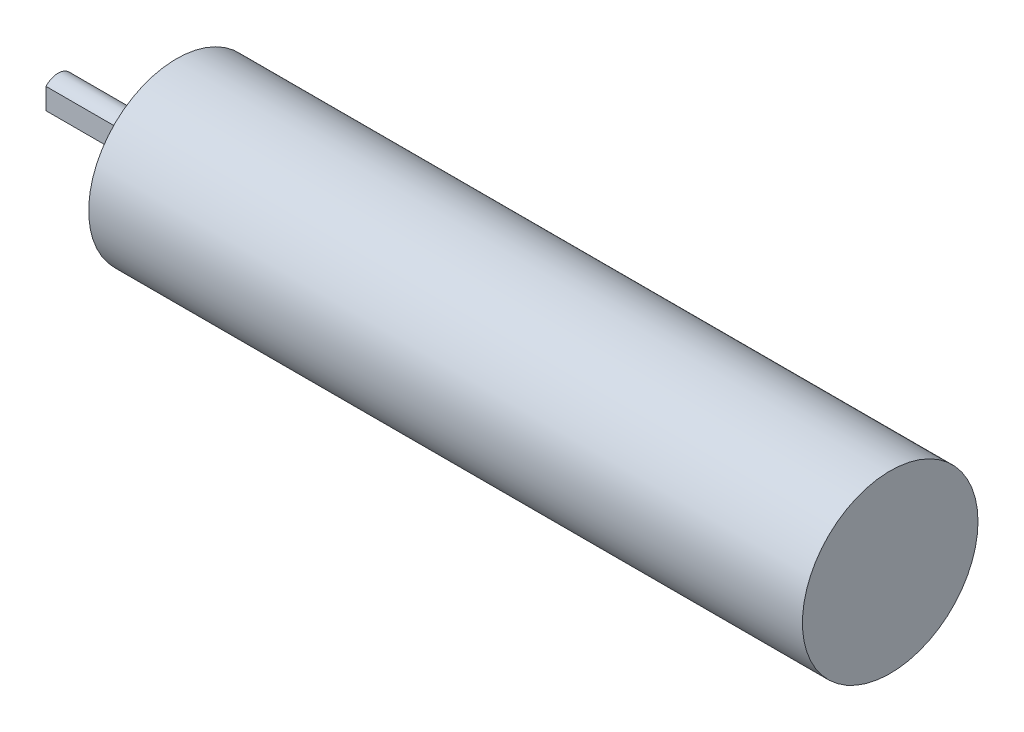
SolidWorks part; units mm, degrees
ref_plane "Front Plane" through (0, 0, 0) normal (0, 0, 1) x (1, 0, 0)
ref_plane "Top Plane" through (0, 0, 0) normal (0, 1, 0) x (1, 0, 0)
ref_plane "Right Plane" through (0, 0, 0) normal (1, 0, 0) x (0, 0, -1)
sketch "Sketch1" plane through (0, 0, 0) normal (0, 0, 1) x (1, 0, 0)
  line L0 (0, 11) -> (0, 0)
  line L1 (0, 0) -> (52.6, 0)
  line L2 (52.6, 0) -> (52.6, 11)
  line L3 (52.6, 11) -> (0, 11)
  line L4 (0, 0) -> (52.6, 0) construction
revolve "Revolve1" add sketch "Sketch1" angle 360 about L4 reverse direction yes
sketch "Sketch2" plane through (0, 0, 0) normal (-1, 0, 0) x (0, 0, 1)
  circle A0 centre (0, 0) radius 5
extrude "Boss-Extrude1" add sketch "Sketch2" along normal blind 1.35
sketch "Sketch3" plane through (-1.35, 0, 0) normal (-1, 0, 0) x (0, 0, 1)
  circle A0 centre (0, 0) radius 3.5
extrude "Boss-Extrude2" add sketch "Sketch3" along normal blind 1.8
sketch "Sketch4" plane through (-3.15, 0, 0) normal (-1, 0, 0) x (0, 0, 1)
  circle A0 centre (0, 0) radius 2
extrude "Boss-Extrude3" add sketch "Sketch4" along normal blind 11.7
ref_plane "Plane1" through (-3.675, 0, 3.675) normal (0.7071, 0, -0.7071) x (0, 1, 0)
sketch "Sketch6" plane through (-14.85, 0, 0) normal (-1, 0, 0) x (0, 0, 1)
  line L0 (1.5, 1.3229) -> (1.5, -1.3229)
  arc A0 (1.5, -1.3229) -> (1.5, 1.3229) centre (0, 0) ccw
extrude "Cut-Extrude1" cut sketch "Sketch6" against normal up to surface up to plane "Plane1"
hole_wizard "Hole1" positions "Sketch8" profile "Sketch7" legacy
sketch "Sketch8" plane through (0, 0, 0) normal (-1, 0, 0) x (0, 0, 1)
  point P0 (7, 0)
sketch "Sketch7" plane through (0, 0, 7) normal (0, 1, 0) x (0, 0, 1)
  line L0 (0, 0) -> (0, 6.5)
  line L1 (0, 6.5) -> (0.975, 6.5)
  line L2 (0.975, 6.5) -> (0.975, 0)
  line L3 (0.975, 0) -> (0, 0)
  line L4 (0, 110) -> (0, -10) construction
  dimension "Diameter" = 1.95
  dimension "Depth" = 6.5
hole_wizard "Hole2" positions "Sketch10" profile "Sketch9" legacy
sketch "Sketch10" plane through (0, 0, 0) normal (-1, 0, 0) x (0, 0, 1)
  point P0 (-3.5, -6.0622)
sketch "Sketch9" plane through (0, -6.0622, -3.5) normal (0, 1, 0) x (0, 0, 1)
  line L0 (0, 0) -> (0, 6.5)
  line L1 (0, 6.5) -> (0.975, 6.5)
  line L2 (0.975, 6.5) -> (0.975, 0)
  line L3 (0.975, 0) -> (0, 0)
  line L4 (0, 110) -> (0, -10) construction
  dimension "Diameter" = 1.95
  dimension "Depth" = 6.5
hole_wizard "Hole3" positions "Sketch12" profile "Sketch11" legacy
sketch "Sketch12" plane through (0, 0, 0) normal (-1, 0, 0) x (0, 0, 1)
  point P0 (-3.5, 6.0622)
sketch "Sketch11" plane through (0, 6.0622, -3.5) normal (0, 1, 0) x (0, 0, 1)
  line L0 (0, 0) -> (0, 6.5)
  line L1 (0, 6.5) -> (0.975, 6.5)
  line L2 (0.975, 6.5) -> (0.975, 0)
  line L3 (0.975, 0) -> (0, 0)
  line L4 (0, 110) -> (0, -10) construction
  dimension "Diameter" = 1.95
  dimension "Depth" = 6.5
hole_wizard "Hole4" positions "Sketch14" profile "Sketch13" legacy
sketch "Sketch14" plane through (52.6, 0, 0) normal (1, 0, 0) x (0, 0, -1)
  point P0 (0, 0)
sketch "Sketch13" plane through (52.6, 0, 0) normal (0, 1, 0) x (0, 0, -1)
  line L0 (0, 0) -> (0, 6.4)
  line L1 (0, 6.4) -> (3.5, 6.4)
  line L2 (3.5, 6.4) -> (3.5, 0)
  line L3 (3.5, 0) -> (0, 0)
  line L4 (0, 110) -> (0, -10) construction
  dimension "Diameter" = 7
  dimension "Depth" = 6.4
hole_wizard "Hole5" positions "Sketch16" profile "Sketch15" legacy
sketch "Sketch16" plane through (52.6, 0, 0) normal (1, 0, 0) x (0, 0, -1)
  point P0 (-8.5, 0)
sketch "Sketch15" plane through (52.6, 0, 8.5) normal (0, 1, 0) x (0, 0, -1)
  line L0 (0, 0) -> (0, 3)
  line L1 (0, 3) -> (1.05, 3)
  line L2 (1.05, 3) -> (1.05, 0)
  line L3 (1.05, 0) -> (0, 0)
  line L4 (0, 110) -> (0, -10) construction
  dimension "Diameter" = 2.1
  dimension "Depth" = 3
hole_wizard "Hole6" positions "Sketch18" profile "Sketch17" legacy
sketch "Sketch18" plane through (52.6, 0, 0) normal (1, 0, 0) x (0, 0, -1)
  point P0 (4.25, -7.3612)
sketch "Sketch17" plane through (52.6, -7.3612, -4.25) normal (0, 1, 0) x (0, 0, -1)
  line L0 (0, 0) -> (0, 3)
  line L1 (0, 3) -> (1.05, 3)
  line L2 (1.05, 3) -> (1.05, 0)
  line L3 (1.05, 0) -> (0, 0)
  line L4 (0, 110) -> (0, -10) construction
  dimension "Diameter" = 2.1
  dimension "Depth" = 3
hole_wizard "Hole7" positions "Sketch20" profile "Sketch19" legacy
sketch "Sketch20" plane through (52.6, 0, 0) normal (1, 0, 0) x (0, 0, -1)
  point P0 (4.25, 7.3612)
sketch "Sketch19" plane through (52.6, 7.3612, -4.25) normal (0, 1, 0) x (0, 0, -1)
  line L0 (0, 0) -> (0, 3)
  line L1 (0, 3) -> (1.05, 3)
  line L2 (1.05, 3) -> (1.05, 0)
  line L3 (1.05, 0) -> (0, 0)
  line L4 (0, 110) -> (0, -10) construction
  dimension "Diameter" = 2.1
  dimension "Depth" = 3
ref_plane "Plane2" through (52.6, 0, 0) normal (1, 0, 0) x (0, 0, -1)
sketch "Sketch25" plane through (52.6, 0, 0) normal (1, 0, 0) x (0, 0, -1)
  circle A0 centre (0, 0) radius 11
extrude "Boss-Extrude4" add sketch "Sketch25" along normal blind 36.83
